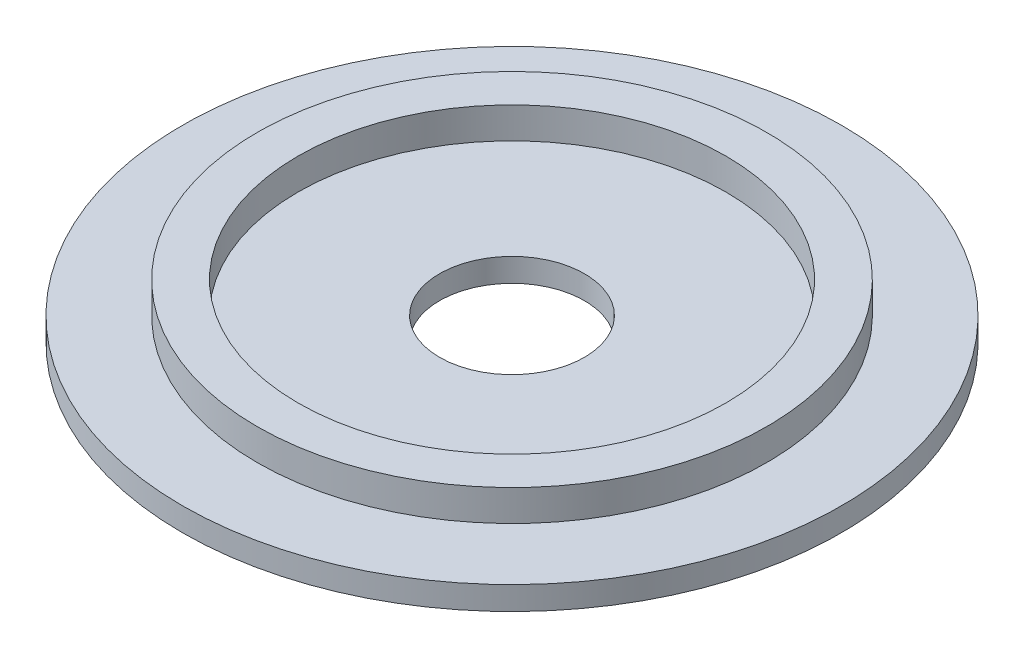
SolidWorks part; units mm, degrees
ref_plane "Front Plane" through (0, 0, 0) normal (0, 0, 1) x (1, 0, 0)
ref_plane "Top Plane" through (0, 0, 0) normal (0, 1, 0) x (1, 0, 0)
ref_plane "Right Plane" through (0, 0, 0) normal (1, 0, 0) x (0, 0, -1)
sketch "Sketch1" plane through (0, 0, 0) normal (0, 1, 0) x (1, 0, 0)
  circle A0 centre (0, 0) radius 4.65
  circle A1 centre (0, 0) radius 21.15
  circle A2 centre (0, 0) radius 16.3532
  circle A3 centre (0, 0) radius 13.729
  dimension "D1" = 9.3
  dimension "D2" = 42.3
extrude "Boss-Extrude1" add sketch "Sketch1" along normal blind 1.5 contours A1 A2 | A2 A3 | A3 A0 region at (-20.5518, 0, 0) region at (-15.8907, 0, 0) region at (-13.3407, 0, 0)
extrude "Boss-Extrude2" add sketch "Sketch1<3>" along normal blind 3.5 contours A2 A3 region at (-15.8907, 0, 0)
sketch "Sketch1<3>" plane through (0, 0, 0) normal (0, 1, 0) x (1, 0, 0) same geometry as "Sketch1"
